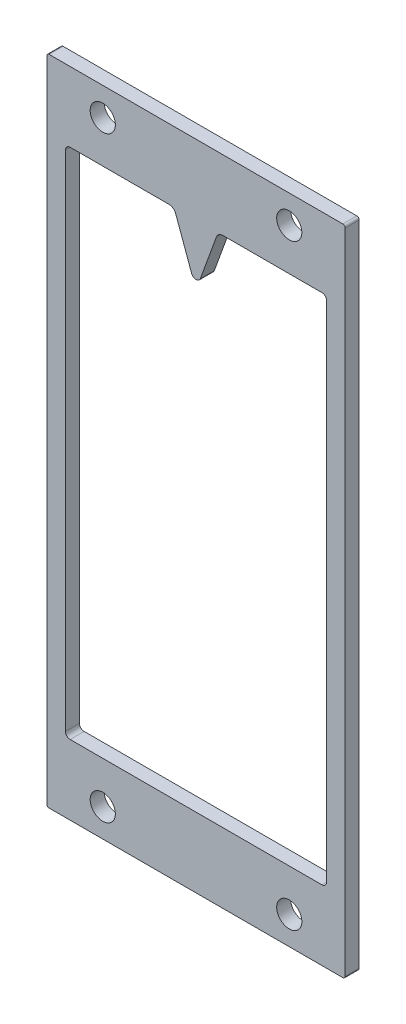
SolidWorks part; units mm, degrees
material "ABS"
ref_plane "Front Plane" through (0, 0, 0) normal (0, 0, 1) x (1, 0, 0)
ref_plane "Top Plane" through (0, 0, 0) normal (0, 1, 0) x (1, 0, 0)
ref_plane "Right Plane" through (0, 0, 0) normal (1, 0, 0) x (0, 0, -1)
sketch "Sketch1" plane through (0, 0, 0) normal (0, 0, 1) x (1, 0, 0)
  line L0 (28, 15) -> (28, 0) construction
  line L1 (0, 0) -> (23.2684, 0)
  line L2 (0, 0) -> (0, -110)
  line L3 (0, -110) -> (56, -110)
  line L4 (56, 0) -> (56, -110)
  line L5 (-4, 15) -> (60, 15)
  line L6 (-4, 15) -> (-4, -125)
  line L7 (-4, -125) -> (60, -125)
  line L8 (60, 15) -> (60, -125)
  line L9 (-4, -55) -> (60, -55) construction
  line L10 (28.9397, -10.4182) -> (32.7316, 0)
  line L11 (27.0603, -10.4182) -> (23.2684, 0)
  line L12 (32.7316, 0) -> (56, 0)
  line L13 (28, -13) -> (28, -125) construction
  circle A0 centre (8, 9) radius 2.6993
  circle A1 centre (48, 9) radius 2.6993
  circle A2 centre (48, -119) radius 2.6993
  circle A3 centre (8, -119) radius 2.6993
  arc A4 (28.9397, -10.4182) -> (27.0603, -10.4182) centre (28, -10.0762) cw
  point P9 (28, -125)
  point P10 (28, -110)
  point P11 (-4, -55)
  point P12 (0, -55)
  dimension "D9" = 1
  dimension "D1" = 56
  dimension "D2" = 110
  dimension "D3" = 64
  dimension "D4" = 140
  dimension "D5" = 12
  dimension "D6" = 6
  dimension "D8" = 13
  dimension "D7" = 20
extrude "Boss-Extrude1" add sketch "Sketch1" along normal blind 3
fillet "Fillet1" radius 1.5 2 edges at (23.2684, 0, 1.5) (32.7316, 0, 1.5)
fillet "Fillet2" radius 0.5 4 edges at (60, -125, 1.5) (-4, -125, 1.5) (60, 15, 1.5) (-4, 15, 1.5)
fillet "Fillet3" radius 1 4 edges at (0, -110, 1.5) (56, -110, 1.5) (56, 0, 1.5) (0, 0, 1.5)
equation "\"Depth\"= 90mm"
equation "\"Height\"= 140mm"
equation "\"Width\"= 64mm"
equation "\"D3@Sketch1\"=\"Width\""
equation "\"D4@Sketch1\"=\"Height\""
